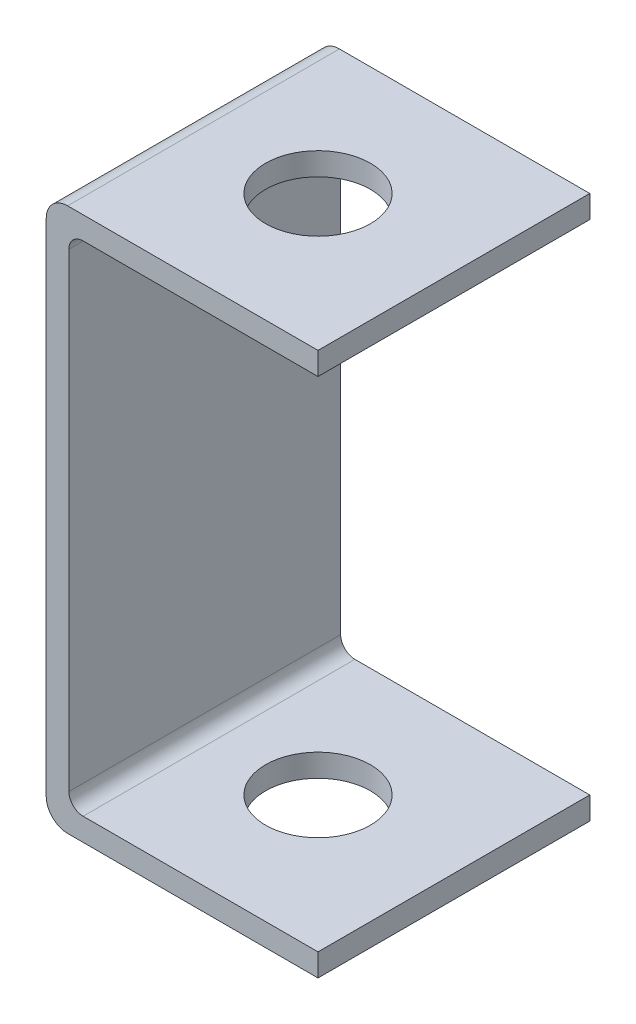
SolidWorks part; units mm, degrees
material "Alumina"
ref_plane "Front Plane" through (0, 0, 0) normal (0, 0, 1) x (1, 0, 0)
ref_plane "Top Plane" through (0, 0, 0) normal (0, 1, 0) x (1, 0, 0)
ref_plane "Right Plane" through (0, 0, 0) normal (1, 0, 0) x (0, 0, -1)
sketch "Sketch1" plane through (0, 0, 0) normal (0, 0, 1) x (1, 0, 0)
  line L0 (-15.875, 73.025) -> (19.05, 73.025)
  line L1 (19.05, 73.025) -> (19.05, 76.2)
  line L2 (19.05, 76.2) -> (-19.05, 76.2)
  line L3 (-19.05, 76.2) -> (-19.05, 0)
  line L4 (-19.05, 0) -> (19.05, 0)
  line L5 (19.05, 0) -> (19.05, 3.175)
  line L6 (19.05, 3.175) -> (-15.875, 3.175)
  line L7 (-15.875, 3.175) -> (-15.875, 73.025)
  point P7 (0, 0)
  dimension "D1" = 3.175
  dimension "D2" = 3.175
  dimension "D3" = 3.175
  dimension "D4" = 38.1
  dimension "D5" = 76.2
extrude "Boss-Extrude1" add sketch "Sketch1" along normal blind 38.1
sketch "Sketch3" plane through (0, 0, 0) normal (0, 1, 0) x (1, 0, 0)
  circle A0 centre (0, -19.05) radius 7.35
  dimension "D2" = 14.7
  dimension "D1" = 19.05
extrude "Cut-Extrude1" cut sketch "Sketch3" along normal through all
fillet "Fillet1" radius 2 2 edges at (-15.875, 3.175, 19.05) (-15.875, 73.025, 19.05)
fillet "Fillet2" radius 3 2 edges at (-19.05, 0, 19.05) (-19.05, 76.2, 19.05)
equation "\"boltDiameter\"= 1in / 2"
equation "\"bracketThickness\"= 1in / 8"
equation "\"D1@Sketch1\"=\"bracketThickness\""
equation "\"D2@Sketch1\"=\"bracketThickness\""
equation "\"D3@Sketch1\"=\"bracketThickness\""
equation "\"D2@Sketch3\"=\"boltDiameter\"+2mm"
equation "\"bracketHeight\"= 3in"
equation "\"D5@Sketch1\"=\"bracketHeight\""
